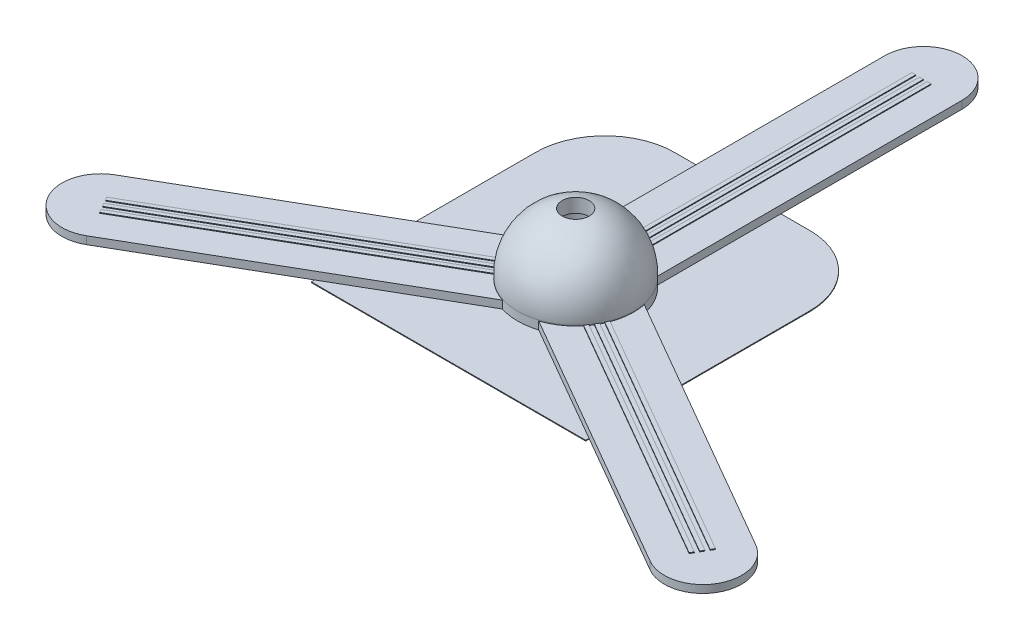
SolidWorks part; units mm, degrees
ref_plane "Front Plane" through (0, 0, 0) normal (0, 0, 1) x (1, 0, 0)
ref_plane "Top Plane" through (0, 0, 0) normal (0, 1, 0) x (1, 0, 0)
ref_plane "Right Plane" through (0, 0, 0) normal (1, 0, 0) x (0, 0, -1)
sketch "Sketch1" plane through (0, 0, 0) normal (0, 1, 0) x (1, 0, 0)
  line L0 (0, -18.1361) -> (0, 31.2383) construction
  line L1 (0, 0) -> (-14.0331, 14.0331) construction
  line L2 (-5, 45) -> (-5, 5.5902)
  line L3 (5, 45) -> (5, 5.5902)
  line L4 (41.4711, -18.1699) -> (7.3412, 1.535)
  line L5 (36.4711, -26.8301) -> (2.3412, -7.1252)
  line L6 (-36.4711, -26.8301) -> (-2.3412, -7.1252)
  line L7 (-41.4711, -18.1699) -> (-7.3412, 1.535)
  arc A0 (7.3412, 1.535) -> (5, 5.5902) centre (0, 0) ccw
  arc A1 (-2.3412, -7.1252) -> (2.3412, -7.1252) centre (0, 0) ccw
  arc A2 (5, 45) -> (-5, 45) centre (0, 45) ccw
  arc A3 (36.4711, -26.8301) -> (41.4711, -18.1699) centre (38.9711, -22.5) ccw
  arc A4 (-41.4711, -18.1699) -> (-36.4711, -26.8301) centre (-38.9711, -22.5) ccw
  arc A5 (-5, 5.5902) -> (-7.3412, 1.535) centre (0, 0) ccw
  point P25 (0, 0)
  dimension "D2" = 15
  dimension "D4" = 10
  dimension "D3" = 45
  dimension "D5" = 3
extrude "Boss-Extrude1" add sketch "Sketch1" along normal blind 1
sketch "Sketch2" plane through (0, 1, 0) normal (0, 1, 0) x (1, 0, 0)
  circle A0 centre (0, 0) radius 7.5
  arc A1 (-5, 5.5902) -> (-7.3412, 1.535) centre (0, 0) ccw construction
extrude "Boss-Extrude2" add sketch "Sketch2" along normal blind 0.1
dome "Dome1" faces to dome 1 distance 8 reverse direction no elliptical dome no face at (0, 1.1, 7.5) parameters "D1"=8
sketch "Sketch3" plane through (0, 0, 0) normal (0, -1, 0) x (1, 0, 0)
  circle A0 centre (0, 0) radius 1.75
  dimension "D1" = 3.5
extrude "Cut-Extrude1" cut sketch "Sketch3" against normal through all
sketch "Sketch5" plane through (0, 0, 0) normal (0, -1, 0) x (1, 0, 0)
  circle A0 centre (0, 0) radius 2.75
  dimension "D1" = 5.5
extrude "Cut-Extrude2" cut sketch "Sketch5" against normal blind 7.1
sketch "Sketch6" plane through (0, 1, 0) normal (0, 1, 0) x (1, 0, 0)
  line L0 (-5, 45) -> (-5, 5.5902) construction
  line L1 (-1.25, 44.7555) -> (-0.75, 44.7555)
  line L2 (-1.25, 44.7555) -> (-1.25, 6.6882)
  line L3 (-1.25, 6.6882) -> (-0.75, 6.6882)
  line L4 (-0.75, 44.7555) -> (-0.75, 6.6882)
  line L5 (0.25, 44.7555) -> (0.25, 6.6882)
  line L6 (-0.25, 6.6882) -> (0.25, 6.6882)
  line L7 (-0.25, 44.7555) -> (0.25, 44.7555)
  line L8 (-0.25, 44.7555) -> (-0.25, 6.6882)
  line L9 (1.25, 44.7555) -> (1.25, 6.6882)
  line L10 (0.75, 6.6882) -> (1.25, 6.6882)
  line L11 (0.75, 44.7555) -> (1.25, 44.7555)
  line L12 (0.75, 44.7555) -> (0.75, 6.6882)
  line L13 (39.3844, -21.2952) -> (6.4171, -2.2616)
  line L14 (39.1344, -21.7282) -> (6.1671, -2.6946)
  line L15 (38.8844, -22.1613) -> (5.9171, -3.1276)
  line L16 (38.6344, -22.5943) -> (5.6671, -3.5606)
  line L17 (38.3844, -23.0273) -> (5.4171, -3.9936)
  line L18 (38.1344, -23.4603) -> (5.1671, -4.4266)
  line L19 (6.4171, -2.2616) -> (6.1671, -2.6946)
  line L20 (5.9171, -3.1276) -> (5.6671, -3.5606)
  line L21 (5.4171, -3.9936) -> (5.1671, -4.4266)
  line L22 (39.3844, -21.2952) -> (39.1344, -21.7282)
  line L23 (38.8844, -22.1613) -> (38.6344, -22.5943)
  line L24 (38.3844, -23.0273) -> (38.1344, -23.4603)
  line L25 (-38.1344, -23.4603) -> (-5.1671, -4.4266)
  line L26 (-38.3844, -23.0273) -> (-5.4171, -3.9936)
  line L27 (-38.6344, -22.5943) -> (-5.6671, -3.5606)
  line L28 (-38.8844, -22.1613) -> (-5.9171, -3.1276)
  line L29 (-39.1344, -21.7282) -> (-6.1671, -2.6946)
  line L30 (-39.3844, -21.2952) -> (-6.4171, -2.2616)
  line L31 (-5.1671, -4.4266) -> (-5.4171, -3.9936)
  line L32 (-5.6671, -3.5606) -> (-5.9171, -3.1276)
  line L33 (-6.1671, -2.6946) -> (-6.4171, -2.2616)
  line L34 (-38.1344, -23.4603) -> (-38.3844, -23.0273)
  line L35 (-38.6344, -22.5943) -> (-38.8844, -22.1613)
  line L36 (-39.1344, -21.7282) -> (-39.3844, -21.2952)
  line L37 (-5, 43.715) -> (5, 43.715) construction
  line L38 (5, 5.5902) -> (5, 45) construction
  point P41 (0, 0)
  point P43 (0, 44.7555)
  point P44 (0, 43.715)
  dimension "D1" = 0.5
  dimension "D2" = 1
  dimension "D3" = 2
  dimension "D4" = 1.5
  dimension "D5" = 2.5
  dimension "D6" = 3
extrude "Boss-Extrude3" add sketch "Sketch6" along normal blind 0.1
sketch "Sketch11" plane through (0, 0, 0) normal (0, -1, 0) x (1, 0, 0)
  line L0 (17.741, 16.4438) -> (-17.759, 16.4438)
  line L1 (-17.759, 16.4438) -> (-17.759, -12.5562)
  line L2 (-8.6862, -21.5559) -> (8.8138, -21.5559)
  line L3 (17.741, -12.5562) -> (17.741, 16.4438)
  line L4 (0, 14.1354) -> (0, -32.7875) construction
  arc A0 (-17.759, -12.5562) -> (-8.6862, -21.5559) centre (-8.759, -12.5562) ccw
  arc A1 (8.8138, -21.5559) -> (17.741, -12.5562) centre (8.741, -12.5562) ccw
extrude "Boss-Extrude6" add sketch "Sketch11" along normal blind 0.1
sketch "Sketch12" plane through (0, 1, 0) normal (0, 1, 0) x (1, 0, 0)
  line L0 (0.25, 44.7555) -> (-0.25, 44.7555) construction
  line L1 (-1.5, 47.9369) -> (1.5, 47.9369)
  line L2 (-1.5, 47.9369) -> (-1.5, 43.9369)
  line L3 (-1.5, 43.9369) -> (1.5, 43.9369)
  line L4 (1.5, 47.9369) -> (1.5, 43.9369)
  line L5 (42.2646, -22.6694) -> (38.8005, -20.6694)
  line L6 (42.2646, -22.6694) -> (40.7646, -25.2675)
  line L7 (40.7646, -25.2675) -> (37.3005, -23.2675)
  line L8 (38.8005, -20.6694) -> (37.3005, -23.2675)
  line L9 (-40.7646, -25.2675) -> (-37.3005, -23.2675)
  line L10 (-40.7646, -25.2675) -> (-42.2646, -22.6694)
  line L11 (-42.2646, -22.6694) -> (-38.8005, -20.6694)
  line L12 (-37.3005, -23.2675) -> (-38.8005, -20.6694)
  point P4 (0, 43.9369)
  point P7 (0, 44.7555)
  point P19 (0, 0)
  dimension "D1" = 3
  dimension "D2" = 4
  dimension "D3" = 3
